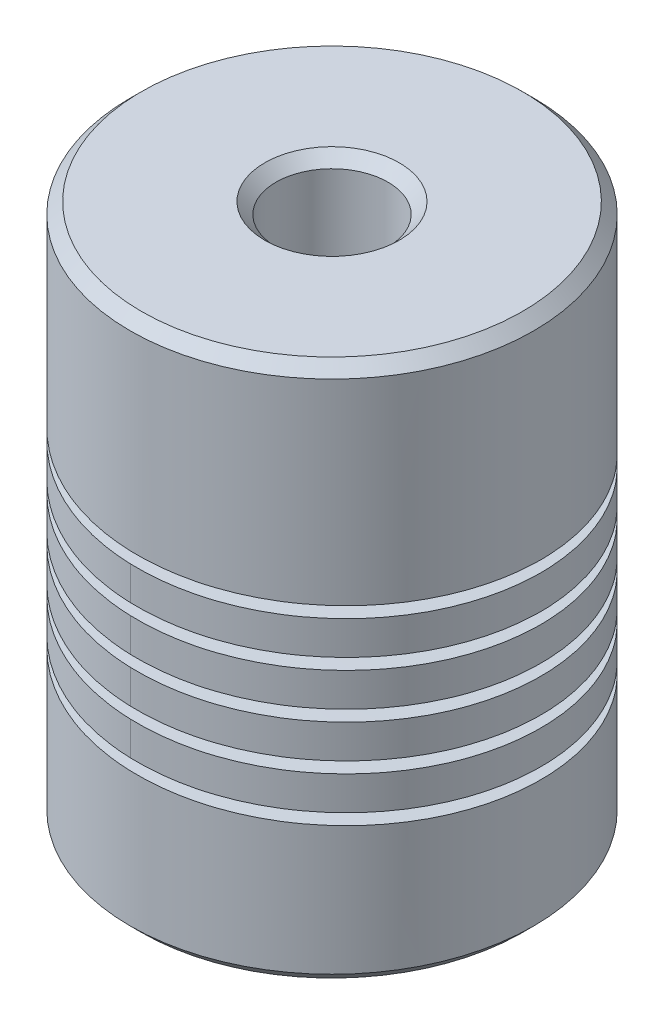
SolidWorks part; units mm, degrees
ref_plane "Front Plane" through (0, 0, 0) normal (0, 0, 1) x (1, 0, 0)
ref_plane "Top Plane" through (0, 0, 0) normal (0, 1, 0) x (1, 0, 0)
ref_plane "Right Plane" through (0, 0, 0) normal (1, 0, 0) x (0, 0, -1)
sketch "Sketch1" plane through (0, 0, 0) normal (0, 1, 0) x (1, 0, 0)
  circle A0 centre (0, 0) radius 9
  dimension "D1" = 18
extrude "Boss-Extrude1" add sketch "Sketch1" along normal blind 24
sketch "Sketch2" plane through (0, 24, 0) normal (0, 1, 0) x (1, 0, 0)
  circle A0 centre (0, 0) radius 2.5
  dimension "D1" = 5
extrude "Cut-Extrude1" cut sketch "Sketch2" against normal through all
sketch "Sketch3" plane through (0, 0, 0) normal (0, -1, 0) x (1, 0, 0)
  circle A0 centre (0, 0) radius 4
  dimension "D1" = 8
extrude "Cut-Extrude2" cut sketch "Sketch3" against normal offset from surface (16 mm away) 8 up to face at (0, 24, 2.5)
chamfer "Chamfer1" distance 0.5 angle 45 4 edges at (0, 24, 2.5) (0, 24, 9) (0, 0, 9) (0, 0, -4)
sketch "Sketch10" plane through (0, 16, 0) normal (0, -1, 0) x (1, 0, 0)
  line L0 (0, -9) -> (0, -4) construction
  line L1 (0, -9) -> (0, -4) construction
  circle A0 centre (0, 0) radius 6.5
  circle A1 centre (0, 0) radius 4 construction
  circle A2 centre (0, 0) radius 9 construction
  point P10 (0, -6.5)
curve "Helix/Spiral1" pitch 2 height 10 turns 5
sketch "Sketch8" plane through (0, 0, 0) normal (1, 0, 0) x (0, 0, -1)
  line L0 (9, 0.5) -> (9, 23.5) construction
  line L1 (9, 16) -> (4, 16)
  line L2 (9, 16) -> (9, 15.5)
  line L3 (9, 15.5) -> (4, 15.5)
  line L4 (4, 16) -> (4, 15.5)
  line L5 (4, 0.5) -> (4, 16) construction
  line L6 (4, 0.5) -> (4, 16) construction
  line L8 (9, 0.5) -> (9, 23.5) construction
  line L9 (4, 15.5) -> (9, 16) construction
  line L10 (-4, 16) -> (4, 16) construction
  dimension "D2" = 0.5
sweep "Cut-Sweep2" cut profiles "Sketch8" path "Helix/Spiral1"
sketch "Sketch11" plane through (0, 0, 0) normal (1, 0, 0) x (0, 0, -1)
  circle A0 centre (0, 2.9729) radius 1.1902
  circle A1 centre (0, 20.3791) radius 1.9654
  dimension "D1" = 3.9309
